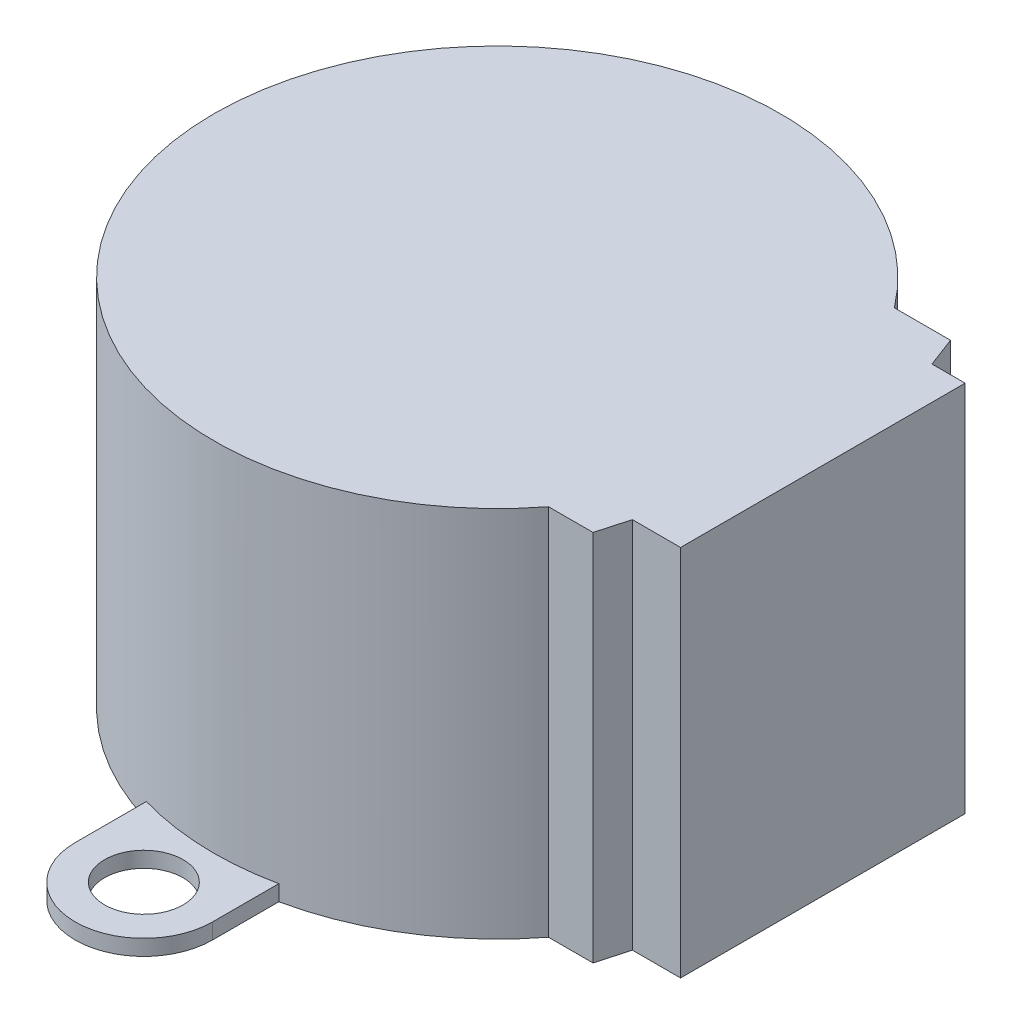
SolidWorks part; units mm, degrees
ref_plane "Front Plane" through (0, 0, 0) normal (0, 0, 1) x (1, 0, 0)
ref_plane "Top Plane" through (0, 0, 0) normal (0, 1, 0) x (1, 0, 0)
ref_plane "Right Plane" through (0, 0, 0) normal (1, 0, 0) x (0, 0, -1)
sketch "Sketch1" plane through (0, 0, 0) normal (0, 1, 0) x (1, 0, 0)
  line L0 (14.3268, 8.7713) -> (14.9056, 7.25)
  line L1 (-0.5062, 17.5) -> (-0.5062, -17.5) construction
  line L2 (-4.0062, 17.5) -> (-4.0062, 13.87)
  line L3 (2.9938, 17.5) -> (2.9938, 14.1232)
  line L4 (16.5938, 7.25) -> (16.5938, -7.25)
  line L5 (-4.0062, -17.5) -> (-4.0062, -13.87)
  line L6 (2.9938, -17.5) -> (2.9938, -14.1232)
  line L7 (11.4669, 8.7713) -> (14.3268, 8.7713)
  line L9 (11.4314, -8.8176) -> (13.7006, -8.8176)
  line L13 (13.7006, -8.8176) -> (14.1389, -7.25)
  line L19 (14.9056, 7.25) -> (16.5938, 7.25)
  line L22 (14.1389, -7.25) -> (16.5938, -7.25)
  circle A0 centre (-9.0922, 0.442) radius 5.334 construction
  arc A1 (11.4669, 8.7713) -> (11.4314, -8.8176) centre (0, 0) ccw
  circle A3 centre (-8.5062, 0) radius 4.6
  circle A4 centre (-8.5062, 0) radius 2.5
  circle A5 centre (-0.5062, 17.5) radius 2
  circle A6 centre (-0.5062, -17.5) radius 2
  arc A8 (-4.0062, -17.5) -> (2.9938, -17.5) centre (-0.5062, -17.5) ccw
  arc A9 (2.9938, 17.5) -> (-4.0062, 17.5) centre (-0.5062, 17.5) ccw
  point P19 (16.5938, 0)
  dimension "D1" = 35
  dimension "D2" = 14.5
  dimension "D5" = 4
  dimension "D6" = 3.5
  dimension "D8" = 9.2
  dimension "D9" = 5
  dimension "D3" = 17.6
  dimension "D4" = 17.1
  dimension "D7" = 8
extrude "Boss-Extrude1" add sketch "Sketch1" along normal blind 19 contours A1 L9 L13 L22 L4 L19 L0 L7 A3 | A4 | A3 A4 region at (1.9974, 0, -0.0117) region at (-12.9761, 0, 0) region at (-8.5062, 0, 0)
extrude "Boss-Extrude2" add sketch "Sketch1<3>" against normal blind 1.6 contours A3 A4 region at (-12.9761, 0, 0)
sketch "Sketch1<3>" plane through (0, 0, 0) normal (0, 1, 0) x (1, 0, 0) same geometry as "Sketch1"
extrude "Boss-Extrude3" add sketch "Sketch1<4>" along normal blind 0.8 contours L3 A9 L2 A1 A5 | L5 A8 L6 A1 A6 region at (-0.5254, 0, -14.5274) region at (-0.5254, 0, 14.5274)
sketch "Sketch1<4>" plane through (0, 0, 0) normal (0, 1, 0) x (1, 0, 0) same geometry as "Sketch1"
extrude "Boss-Extrude4" add sketch "Sketch1<5>" against normal blind 4 contours A4 region at (-8.5062, 0, 0)
sketch "Sketch1<5>" plane through (0, 0, 0) normal (0, 1, 0) x (1, 0, 0) same geometry as "Sketch1"
sketch "Sketch5" plane through (0, -4, 0) normal (0, -1, 0) x (1, 0, 0)
  line L0 (-10.5062, 1.5) -> (-6.5062, 1.5)
  line L1 (-10.5062, -1.5) -> (-6.5062, -1.5)
  line L2 (-9.9683, 1.5) -> (-9.9683, -1.5) construction
  circle A1 centre (-8.5062, 0) radius 2.5
  circle A2 centre (-8.5062, 0) radius 2.5
  point P9 (-9.9683, 0)
  circle M2 centre (-8.5062, 0) radius 2.5
  dimension "D1" = 0
extrude "Boss-Extrude5" add sketch "Sketch5" along normal blind 6 contours L2 L0 L1 M2 | L0 L2 L1 M2 region at (-10.4198, -4, 0) region at (-8.0641, -4, 0)
fillet "Fillet1" radius 1 1 edges
fillet "Fillet2" radius 1 1 edges
